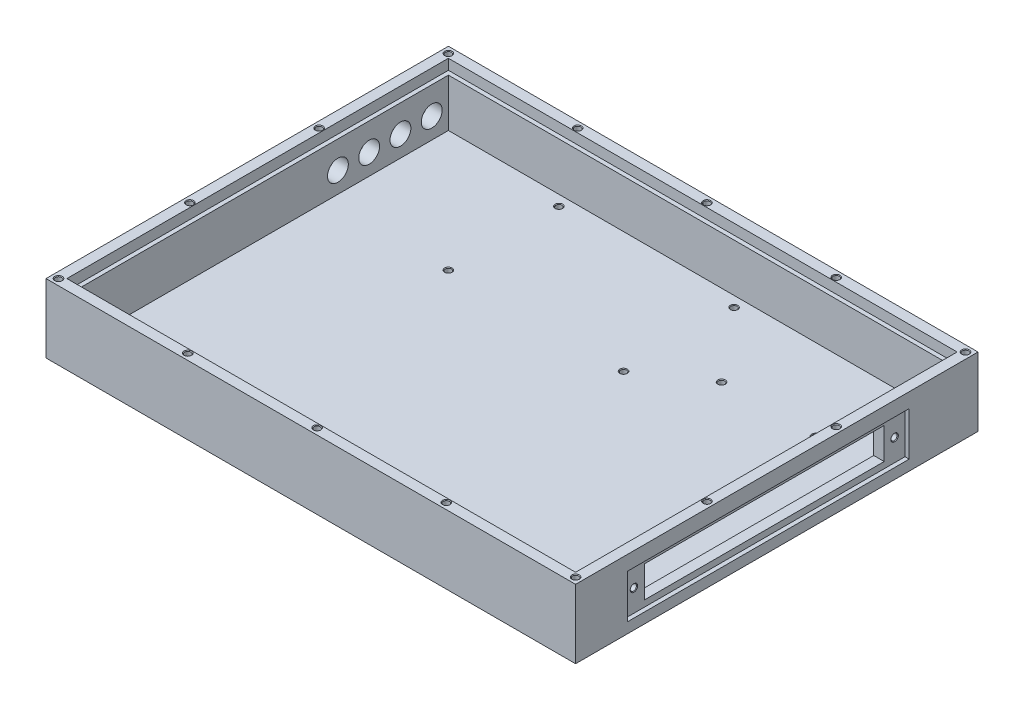
SolidWorks part; units mm, degrees
material "5454-H111"
ref_plane "Front Plane" through (0, 0, 0) normal (0, 0, 1) x (1, 0, 0)
ref_plane "Top Plane" through (0, 0, 0) normal (0, 1, 0) x (1, 0, 0)
ref_plane "Right Plane" through (0, 0, 0) normal (1, 0, 0) x (0, 0, -1)
sketch "Sketch1" plane through (0, 0, 0) normal (0, 1, 0) x (1, 0, 0)
  line L1 (127, -96.5) -> (-127, -96.5)
  line L2 (127, -96.5) -> (127, 96.5)
  line L3 (127, 96.5) -> (-127, 96.5)
  line L4 (-127, -96.5) -> (-127, 96.5)
  line L5 (127, -96.5) -> (-127, 96.5) construction
  line L6 (127, 96.5) -> (-127, -96.5) construction
  point P0 (0, 0)
  dimension "D1" = 254
  dimension "D2" = 193
extrude "Boss-Extrude1" add sketch "Sketch1" along normal blind 33
sketch "Sketch2" plane through (0, 33, 0) normal (0, 1, 0) x (1, 0, 0)
  line L0 (127, 96.5) -> (-127, 96.5) construction
  line L1 (-120, 89.5) -> (120, 89.5)
  line L2 (-120, 89.5) -> (-120, -89.5)
  line L3 (-120, -89.5) -> (120, -89.5)
  line L4 (120, 89.5) -> (120, -89.5)
  line L5 (-127, 96.5) -> (-127, -96.5) construction
  line L6 (127, -96.5) -> (127, 96.5) construction
  line L7 (-127, -96.5) -> (127, -96.5) construction
  dimension "D1" = 7
  dimension "D2" = 7
  dimension "D3" = 7
  dimension "D4" = 7
extrude "Cut-Extrude1" cut sketch "Sketch2" against normal blind 28
sketch "Sketch3" plane through (0, 33, 0) normal (0, 1, 0) x (1, 0, 0)
  line L1 (122, -91.5) -> (-122, -91.5)
  line L2 (122, -91.5) -> (122, 91.5)
  line L3 (122, 91.5) -> (-122, 91.5)
  line L4 (-122, -91.5) -> (-122, 91.5)
  line L5 (122, -91.5) -> (-122, 91.5) construction
  line L6 (122, 91.5) -> (-122, -91.5) construction
  point P0 (0, 0)
  dimension "D1" = 244
  dimension "D2" = 183
extrude "Cut-Extrude2" cut sketch "Sketch3" against normal blind 5
sketch "Sketch4" plane through (-120, 0, 0) normal (1, 0, 0) x (0, 0, -1)
  line L1 (89.5, 5) -> (-89.5, 5) construction
  line L2 (96.5, 33) -> (96.5, 0) construction
  circle A0 centre (81.5, 15) radius 5
  circle A2 centre (66.5, 15) radius 5
  circle A3 centre (51.5, 15) radius 5
  circle A4 centre (36.5, 15) radius 5
  dimension "D3" = 10
  dimension "D4" = 4
  dimension "D5" = 15
  dimension "D1" = 15
  dimension "D2" = 10
extrude "Cut-Extrude3" cut sketch "Sketch4" against normal through all
sketch "Sketch7" plane through (127, 0, 0) normal (1, 0, 0) x (0, 0, -1)
  line L0 (-96.5, 33) -> (-96.5, 0) construction
  line L1 (-71.5, 5) -> (63.5, 5)
  line L2 (-71.5, 5) -> (-71.5, 26)
  line L3 (-71.5, 26) -> (63.5, 26)
  line L4 (63.5, 5) -> (63.5, 26)
  line L5 (-96.5, 0) -> (96.5, 0) construction
  dimension "D1" = 25
  dimension "D2" = 5
  dimension "D3" = 135
  dimension "D4" = 21
extrude "Cut-Extrude5" cut sketch "Sketch7" against normal blind 2
sketch "Sketch8" plane through (125, 0, 0) normal (1, 0, 0) x (0, 0, -1)
  line L0 (-71.5, 5) -> (63.5, 5) construction
  line L5 (-71.5, 26) -> (-71.5, 5) construction
  line L6 (-61.5, 8) -> (53.5, 23) construction
  line L16 (63.5, 5) -> (63.5, 26) construction
  line L47 (-61.5, 23) -> (53.5, 8) construction
  line L53 (53.5, 8) -> (-61.5, 23) construction
  line L54 (53.5, 23) -> (-61.5, 8) construction
  line L55 (53.5, 8) -> (-61.5, 8)
  line L56 (53.5, 8) -> (53.5, 23)
  line L57 (53.5, 23) -> (-61.5, 23)
  line L58 (-61.5, 8) -> (-61.5, 23)
  line L59 (53.5, 8) -> (-61.5, 23) construction
  line L60 (53.5, 23) -> (-61.5, 8) construction
  point P6 (-4, 15.5)
  point P38 (-4, 15.5)
  dimension "D1" = 10
  dimension "D2" = 15
  dimension "D3" = 10
  dimension "D4" = 3
extrude "Cut-Extrude6" cut sketch "Sketch8" against normal up to next
sketch "Sketch10" plane through (0, 33, 0) normal (0, 1, 0) x (1, 0, 0)
  line L0 (-127, 96.5) -> (-127, -96.5) construction
  line L1 (127, 96.5) -> (-127, 96.5) construction
  circle A0 centre (-124, 93.5) radius 1.5
  dimension "D1" = 3
  dimension "D2" = 3
  dimension "D3" = 3
extrude "Cut-Extrude8" cut sketch "Sketch10" against normal blind 3
pattern_linear "LPattern9" count 5 spacing 62 along (1, 0, 0) count 2 spacing 187 along (0, 0, 1) of "Cut-Extrude8"
pattern_linear "LPattern10" count 3 spacing 62 along (0, 0, 1) count 2 spacing 248 along (1, 0, 0) of "Cut-Extrude8"
sketch "Sketch9" plane through (125, 0, 0) normal (1, 0, 0) x (0, 0, -1)
  line L0 (-4, 26) -> (-4, 5) construction
  line L1 (-71.5, 5) -> (63.5, 5) construction
  line L2 (63.5, 26) -> (-71.5, 26) construction
  line L3 (-71.5, 26) -> (-71.5, 5) construction
  line L4 (-71.5, 5) -> (63.5, 5) construction
  circle A0 centre (-66.5, 15.5) radius 1.5
  circle A2 centre (58.5, 15.5) radius 1.5
  dimension "D1" = 10.5
  dimension "D3" = 3
  dimension "D2" = 5
extrude "Cut-Extrude7" cut sketch "Sketch9" against normal blind 3
sketch "Sketch6" plane through (0, 5, 0) normal (0, 1, 0) x (1, 0, 0)
  line L0 (120, -89.5) -> (120, 89.5) construction
  line L1 (-120, -89.5) -> (120, -89.5) construction
  circle A3 centre (95, -74.5) radius 1.5
  dimension "D1" = 25
  dimension "D2" = 15
extrude "Cut-Extrude4" cut sketch "Sketch6" against normal blind 3
pattern_linear "LPattern11" count 2 spacing 125 along (0, 0, -1) count 2 spacing 45 along (-1, 0, 0) of "Cut-Extrude4"
sketch "Sketch11" plane through (0, 5, 0) normal (0, 1, 0) x (1, 0, 0)
  line L0 (-120, 89.5) -> (-120, -89.5) construction
  line L1 (-120, 89.5) -> (120, 89.5) construction
  circle A0 centre (22, 84.5) radius 1.5
  dimension "D1" = 3
  dimension "D2" = 142
  dimension "D3" = 5
extrude "Cut-Extrude9" cut sketch "Sketch11" against normal blind 3
pattern_linear "LPattern12" count 2 spacing 84 along (-1, 0, 0) count 2 spacing 53 along (0, 0, 1) of "Cut-Extrude9"
chamfer "Chamfer2" distance 0.3 angle 45 24 edges at (125, 15.5, -57) (62, 33, 95) (0, 33, 95) (-62, 33, 95) (-124, 33, 95) (-124, 33, 32) (-62, 5, -30) (-124, 33, -30) (-124, 33, -92) (-62, 5, -83) (-62, 33, -92) (0, 33, -92) (22, 5, -83) (22, 5, -30) (50, 5, -49) (62, 33, -92) (95, 5, -49) (124, 33, -92) (124, 33, -30) (124, 33, 32) (124, 33, 95) (50, 5, 76) (95, 5, 76) (125, 15.5, 65)
